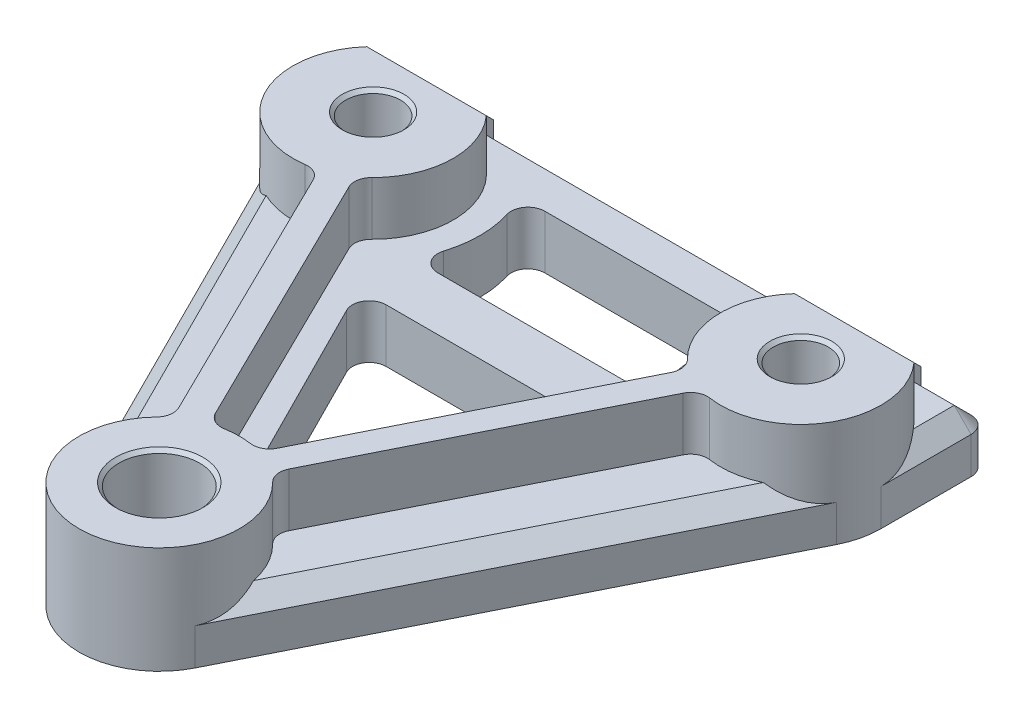
SolidWorks part; units mm, degrees
ref_plane "Front Plane" through (0, 0, 0) normal (0, 0, 1) x (1, 0, 0)
ref_plane "Top Plane" through (0, 0, 0) normal (0, 1, 0) x (1, 0, 0)
ref_plane "Right Plane" through (0, 0, 0) normal (1, 0, 0) x (0, 0, -1)
sketch "Sketch1" plane through (0, 0, 0) normal (0, 1, 0) x (1, 0, 0)
  line L0 (0, -50.8) -> (0, 0) construction
  line L1 (25.4, 0) -> (-25.4, 0) construction
  line L2 (34.925, 0) -> (34.925, 12.7)
  line L3 (-33.9194, -4.2597) -> (-8.5194, -55.0597)
  line L4 (-34.925, 0) -> (-34.925, 12.7)
  line L5 (14.4015, 6.35) -> (-14.4015, 6.35)
  line L6 (-14.4015, -12.7) -> (14.4015, -12.7)
  line L7 (14.4015, -6.35) -> (-14.4015, -6.35)
  line L8 (0, -41.275) -> (-14.4015, -12.7)
  line L9 (0, -41.275) -> (14.4015, -12.7)
  line L10 (34.925, 12.7) -> (-34.925, 12.7)
  line L11 (33.9194, -4.2597) -> (8.5194, -55.0597)
  circle A0 centre (-25.4, 0) radius 3.175 construction
  circle A1 centre (25.4, 0) radius 3.175 construction
  circle A2 centre (0, -50.8) radius 4.7625 construction
  arc A3 (-8.5194, -55.0597) -> (8.5194, -55.0597) centre (0, -50.8) ccw
  arc A4 (-14.4015, 6.35) -> (-14.4015, -6.35) centre (-25.4, 0) cw
  arc A5 (14.4015, 6.35) -> (14.4015, -6.35) centre (25.4, 0) ccw
  arc A8 (-34.925, 0) -> (-33.9194, -4.2597) centre (-25.4, 0) ccw
  arc A9 (34.925, 0) -> (33.9194, -4.2597) centre (25.4, 0) cw
  point P5 (0, 0)
  point P27 (0, 12.7)
  dimension "D3" = 19.05
  dimension "D4" = 19.05
  dimension "D5" = 6.35
  dimension "D6" = 12.7
  dimension "D1" = 50.8
  dimension "D2" = 50.8
extrude "Boss-Extrude1" add sketch "Sketch1" along normal blind 6.35
hole_wizard "F (0.257) Diameter Hole2" positions "Sketch7" profile "Sketch6" hole size "F" standard "ANSI Inch" end condition through all
sketch "Sketch7" plane through (0, 6.35, 0) normal (0, 1, 0) x (1, 0, 0)
  line L0 (-34.925, 0) -> (34.925, 0) construction
  line L1 (0, 12.7) -> (0, -60.325) construction
  line L2 (34.925, 12.7) -> (-34.925, 12.7) construction
  arc A0 (-8.5194, -55.0597) -> (8.5194, -55.0597) centre (0, -50.8) ccw construction
  point P13 (-25.4, 0)
  point P16 (25.4, 0)
  dimension "D1" = 25.4
sketch "Sketch6" plane through (-25.4, 6.35, 0) normal (1, 0, 0) x (0, 0, 1)
  line L0 (0, 0) -> (0, 6.35)
  line L1 (0, 6.35) -> (3.2639, 6.35)
  line L2 (3.2639, 6.35) -> (3.2639, 0)
  line L5 (3.2639, 0) -> (0, 0)
  line L11 (0, -6.35) -> (0, 107.95) construction
  dimension "Thru Hole Dia." = 6.5278
  dimension "Thru Hole Depth" = 6.35
fillet "Fillet1" radius 2 9 edges at (0, 3.175, 41.275) (14.4015, 3.175, 12.7) (-14.4015, 3.175, 12.7) (-14.4015, 3.175, -6.35) (-14.4015, 3.175, 6.35) (14.4015, 3.175, -6.35) (14.4015, 3.175, 6.35) (34.925, 3.175, -12.7) (-34.925, 3.175, -12.7)
hole_wizard "V (0.377) Diameter Hole2" positions "Sketch11" profile "Sketch10" hole size "V" standard "ANSI Inch" end condition through all
sketch "Sketch11" plane through (0, 6.35, 0) normal (0, 1, 0) x (1, 0, 0)
  point P0 (0, -50.8)
  dimension "D1" = 50.8
sketch "Sketch10" plane through (0, 6.35, 50.8) normal (1, 0, 0) x (0, 0, 1)
  line L0 (0, 0) -> (0, 6.35)
  line L1 (0, 6.35) -> (4.7879, 6.35)
  line L2 (4.7879, 6.35) -> (4.7879, 0)
  line L5 (4.7879, 0) -> (0, 0)
  line L11 (0, -6.35) -> (0, 107.95) construction
  dimension "Thru Hole Dia." = 9.5758
  dimension "Thru Hole Depth" = 6.35
sketch "Sketch12" plane through (0, 6.35, 0) normal (0, 1, 0) x (1, 0, 0)
  line L0 (0, 12.7) -> (0, -60.325) construction
  line L1 (32.925, 12.7) -> (-32.925, 12.7) construction
  circle A0 centre (-25.4, 0) radius 3.2639
  circle A1 centre (-25.4, 0) radius 9.525
  arc A2 (-8.5194, -55.0597) -> (8.5194, -55.0597) centre (0, -50.8) ccw construction
  circle A3 centre (25.4, 0) radius 3.2639
  circle A4 centre (25.4, 0) radius 9.525
  circle A5 centre (0, -50.8) radius 4.7879
  circle A6 centre (0, -50.8) radius 9.525
  dimension "D1" = 19.05
extrude "Boss-Extrude2" add sketch "Sketch12" along normal blind 6.35
sketch "Sketch13" plane through (0, 6.35, 0) normal (0, 1, 0) x (1, 0, 0)
  line L0 (-25.4, 0) -> (-25.4, 12.7) construction
  line L1 (32.925, 12.7) -> (-32.925, 12.7) construction
  line L2 (0, 12.7) -> (0, -60.325) construction
  line L3 (-23.8125, 4.875) -> (-26.9875, 4.875)
  line L4 (-26.9875, 4.875) -> (-26.9875, 12.7)
  line L5 (-26.9875, 12.7) -> (-23.8125, 12.7)
  line L6 (-23.8125, 12.7) -> (-23.8125, 4.875)
  line L7 (23.8125, 4.875) -> (26.9875, 4.875)
  line L8 (26.9875, 12.7) -> (23.8125, 12.7)
  line L9 (26.9875, 4.875) -> (26.9875, 12.7)
  line L10 (23.8125, 12.7) -> (23.8125, 4.875)
  line L11 (-25.4, 0) -> (25.4, 0) construction
  circle A0 centre (0, -50.8) radius 9.525 construction
  point P13 (-25.4, 4.875)
extrude "Boss-Extrude3" add sketch "Sketch13" along normal blind 6.35
chamfer "Chamfer1" distance 0.4 angle 45 2 edges at (25.4, 12.7, -3.2639) (-25.4, 12.7, 3.2639)
sketch "Sketch15" plane through (0, 6.35, 0) normal (0, 1, 0) x (1, 0, 0)
  line L0 (0, -50.8) -> (25.4, 0) construction
  line L1 (0, -50.8) -> (-25.4, 0) construction
  line L2 (-0.2053, -50.3895) -> (0, 12.7) construction
  line L3 (23.8125, 12.7) -> (-23.8125, 12.7) construction
  line L4 (4.6818, -44.9861) -> (1.842, -43.5662)
  line L5 (1.842, -43.5662) -> (21.7207, -3.8089)
  line L6 (4.6818, -44.9861) -> (24.5605, -5.2288)
  line L7 (21.7207, -3.8089) -> (24.5605, -5.2288)
  line L8 (-5.0571, -44.9544) -> (-24.6766, -5.0686)
  line L9 (-2.2081, -43.553) -> (-21.8276, -3.6672)
  line L10 (-5.0571, -44.9544) -> (-2.2081, -43.553)
  line L11 (-21.8276, -3.6672) -> (-24.6766, -5.0686)
  point P13 (3.2619, -44.2762)
  dimension "D2" = 44.45
extrude "Boss-Extrude4" add sketch "Sketch15" along normal blind 6.35
chamfer "Chamfer2" distance 0.4 angle 45 1 edges at (0, 12.7, 55.5879)
ref_plane "Plane1" through (21.7399, 0, 10.87) normal (0.8944, 0, 0.4472) x (0.4472, 0, -0.8944)
ref_plane "Plane2" through (-21.8766, 0, 10.7609) normal (-0.8973, 0, 0.4414) x (0.4414, 0, 0.8973)
fillet "Fillet4" radius 2 14 edges at (23.8125, 9.525, -9.3918) (26.9875, 9.525, -9.3918) (-26.9875, 9.525, -9.3918) (-23.8125, 9.525, -9.3918) (19.78, 9.525, 7.6903) (2.7802, 9.525, 41.6898) (22.6198, 9.525, 9.1102) (5.62, 9.525, 43.1097) (-3.0774, 9.525, 41.7858) (-19.8306, 9.525, 7.7271) (-5.8711, 9.525, 43.2996) (-22.6797, 9.525, 9.1283)
chamfer "Chamfer3" distance 6.35 angle 45 2 edges at (25.4, 12.7, -12.7) (-25.4, 12.7, -12.7)
chamfer "Chamfer5" distance 2 angle 45 9 edges at (21.2194, 6.35, 29.6597) (29.9563, 6.35, -12.7) (34.3392, 6.35, -12.1142) (34.925, 6.35, -5.35) (0, 6.35, -12.7) (-29.9562, 6.35, -12.7) (-34.3392, 6.35, -12.1142)
sketch "Sketch18" plane through (0, 6.35, 0) normal (0, 1, 0) x (1, 0, 0)
  line L1 (0, 6.35) -> (0, -6.35) construction
  line L2 (-25.4, 6.9932) -> (-31.4562, 3.4966)
  line L3 (-31.4562, 3.4966) -> (-31.4562, -3.4966)
  line L4 (-31.4562, -3.4966) -> (-25.4, -6.9932)
  line L5 (-25.4, -6.9932) -> (-19.3437, -3.4966)
  line L6 (-19.3437, -3.4966) -> (-19.3437, 3.4966)
  line L7 (-19.3437, 3.4966) -> (-25.4, 6.9932)
  line L8 (11.3584, 6.35) -> (-11.3584, 6.35) construction
  line L9 (-11.3584, -6.35) -> (11.3584, -6.35) construction
  line L10 (31.4562, 3.4966) -> (31.4562, -3.4966)
  line L11 (31.4562, -3.4966) -> (25.4, -6.9932)
  line L12 (25.4, -6.9932) -> (19.3438, -3.4966)
  line L13 (19.3438, -3.4966) -> (19.3438, 3.4966)
  line L14 (25.4, 6.9932) -> (31.4562, 3.4966)
  line L15 (19.3438, 3.4966) -> (25.4, 6.9932)
  circle A1 centre (-25.4, 0) radius 6.0562 construction
  dimension "D1" = 25.4
extrude "Cut-Extrude5" [suppressed] cut sketch "Sketch18" along normal blind 6.35
chamfer "Chamfer6" [suppressed] distance 0.4 angle 45
chamfer "Chamfer7" [suppressed] distance 0.4 angle 45
